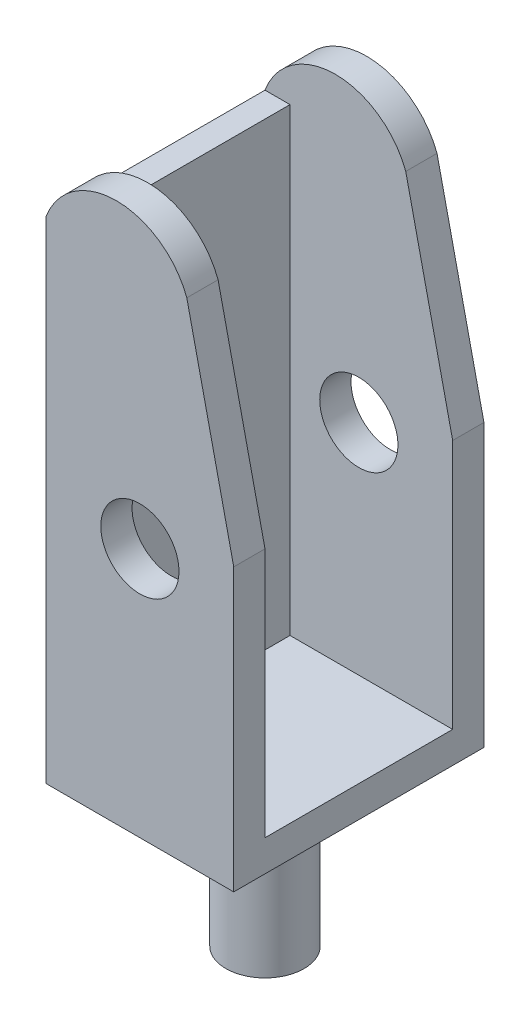
SolidWorks part; units mm, degrees
ref_plane "Front Plane" through (0, 0, 0) normal (0, 0, 1) x (1, 0, 0)
ref_plane "Top Plane" through (0, 0, 0) normal (0, 1, 0) x (1, 0, 0)
ref_plane "Right Plane" through (0, 0, 0) normal (1, 0, 0) x (0, 0, -1)
ref_plane "Plane1" through (0, 0, 30) normal (0, 0, 1) x (1, 0, 0)
sketch "Sketch2" plane through (0, 0, 30) normal (0, 0, 1) x (1, 0, 0)
  line L0 (0, 0) -> (0, -80) construction
  line L1 (0, -80) -> (30, -80)
  line L2 (0, -80) -> (-30, -80)
  line L3 (-30, -80) -> (-30, 77)
  line L4 (30, -80) -> (30, 10)
  line L5 (15, 77) -> (30, 10)
  circle A0 centre (0, 0) radius 12.5 construction
  arc A1 (15, 77) -> (-30, 77) centre (-7.5, 68.6484) ccw
  dimension "D1" = 25
  dimension "D2" = 80
  dimension "D3" = 30
  dimension "D4" = 30
  dimension "D5" = 157
  dimension "D6" = 90
  dimension "D7" = 45
extrude "Boss-Extrude1" add sketch "Sketch2" along normal blind 10
sketch "Sketch4" plane through (0, -80, 0) normal (0, -1, 0) x (1, 0, 0)
  line L0 (-30, 30) -> (30, 30) construction
  line L1 (-30, 30) -> (30, 30)
  line L2 (30, 30) -> (30, -30)
  line L3 (30, -30) -> (-30, -30)
  line L4 (-30, -30) -> (-30, 30)
  dimension "D1" = 60
extrude "Boss-Extrude2" add sketch "Sketch4" against normal blind 10
mirror "Mirror3" about plane through (0, 0, 0) normal (0, 0, 1) of "Boss-Extrude1"
sketch "Sketch5" plane through (-30, 0, 0) normal (-1, 0, 0) x (0, 0, 1)
  line L0 (-30, 77) -> (-30, -70) construction
  line L1 (-30, 77) -> (-30, -70)
  line L2 (30, 77) -> (30, -70) construction
  line L3 (30, 77) -> (30, -70)
  line L4 (-30, 77) -> (30, 77)
  line L5 (-30, -70) -> (30, -70)
extrude "Boss-Extrude3" add sketch "Sketch5" against normal blind 8
sketch "Sketch6" plane through (0, 0, 0) normal (0, 0, 1) x (1, 0, 0)
  circle A0 centre (0, 0) radius 12.5
  dimension "D1" = 25
extrude "Cut-Extrude1" cut sketch "Sketch6" against normal mid plane 144
sketch "Sketch7" plane through (0, -80, 0) normal (0, -1, 0) x (1, 0, 0)
  line L0 (-30, 0) -> (30, 0) construction
  line L1 (-30, 40) -> (-30, -40) construction
  line L2 (30, 40) -> (30, -40) construction
  line L3 (0, 40) -> (0, -40) construction
  line L4 (-30, 40) -> (30, 40) construction
  line L5 (-30, -40) -> (30, -40) construction
  circle A0 centre (0, 0) radius 12.5
  dimension "D1" = 25
extrude "Boss-Extrude4" add sketch "Sketch7" along normal blind 50
ref_axis "Axis1" through (0, 0, -40) along (0, 0, 1)
